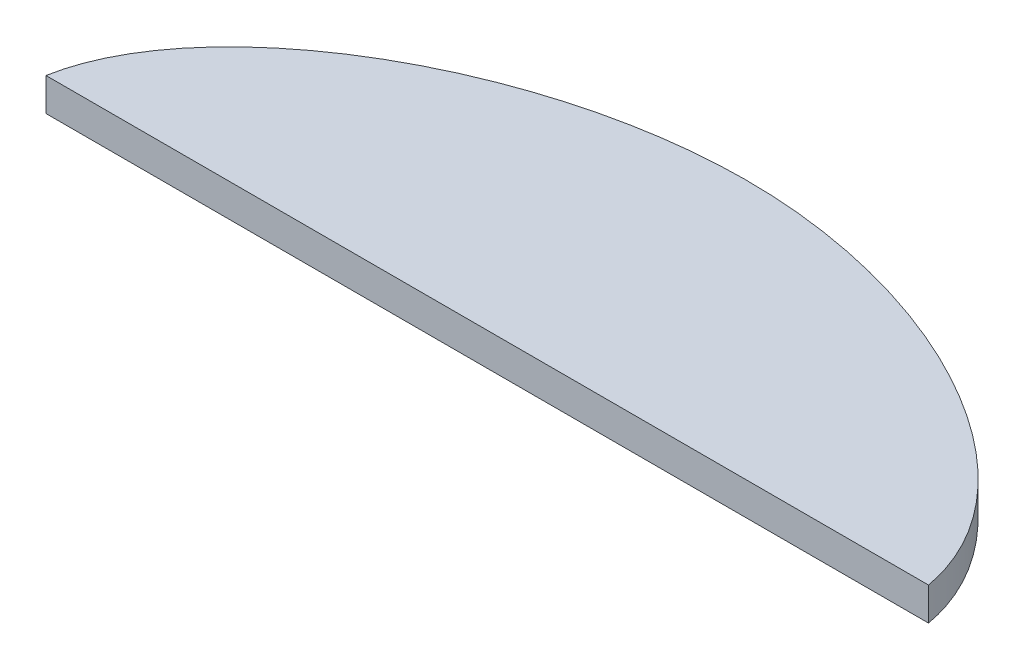
SolidWorks part; units mm, degrees
ref_plane "Front Plane" through (0, 0, 0) normal (0, 0, 1) x (1, 0, 0)
ref_plane "Top Plane" through (0, 0, 0) normal (0, 1, 0) x (1, 0, 0)
ref_plane "Right Plane" through (0, 0, 0) normal (1, 0, 0) x (0, 0, -1)
sketch "Sketch1" plane through (0, 0, 0) normal (0, 1, 0) x (1, 0, 0)
  line L0 (0, 0) -> (85, 0)
  line L1 (42.5, 0) -> (42.5, 25)
  line L2 (104.8351, -112.4906) -> (65.1649, 112.4906) construction
  line L3 (16.2479, 92.1462) -> (-16.2479, -92.1462) construction
  spline S0 degree 3 poles (0, 0) (2.3153, 13.1308) (42.5, 36.8692) (82.6847, 13.1308) (85, 0) knots 0 0 0 0 0.5 1 1 1 1
  dimension "D4" = 80
  dimension "D5" = 40
  dimension "D6" = 40
  dimension "D1" = 85
  dimension "D2" = 25
  dimension "D3" = 80
extrude "Boss-Extrude1" add sketch "Sketch1" along normal blind 3.175 contours S0 L0 L1 | S0 L1 L0 region at (25.1076, 0, -10.3687) region at (59.8924, 0, -10.3687)
